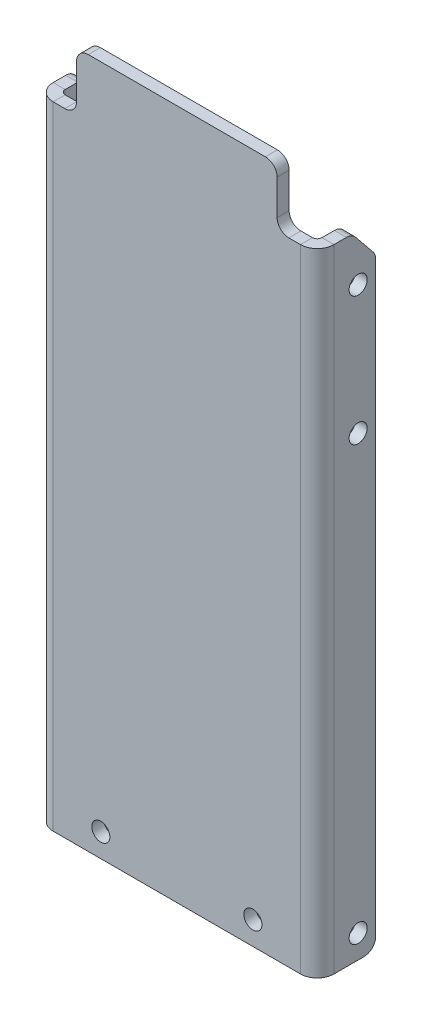
SolidWorks part; units mm, degrees
note: The reader was unsure of these and kept them because the rebuilt part matched: flange length of "Edge-Flange1".
material "5052-H32"
ref_plane "Front Plane" through (0, 0, 0) normal (0, 0, 1) x (1, 0, 0)
ref_plane "Top Plane" through (0, 0, 0) normal (0, 1, 0) x (1, 0, 0)
ref_plane "Right Plane" through (0, 0, 0) normal (1, 0, 0) x (0, 0, -1)
sketch "Sketch1" plane through (0, 0, 0) normal (0, 0, 1) x (1, 0, 0)
  line L0 (-38.1, 0) -> (38.1, 0) construction
  line L1 (-38.1, 124.1214) -> (38.1, 124.1214)
  line L2 (-38.1, 124.1214) -> (-38.1, -47.3286)
  line L3 (-38.1, -47.3286) -> (38.1, -47.3286)
  line L4 (38.1, 124.1214) -> (38.1, -47.3286)
  point P6 (0, 0)
  dimension "D1" = 47.3286
  dimension "D2" = 76.2
  dimension "D3" = 171.45
base flange "Base-Flange1" sketch "Sketch1" thickness 3.2639 reverse thickness direction no parameters "D1"=1.27
edge flange "Edge-Flange1" sketch "Sketch27" flange profiles "Sketch27", "Sketch28" flange angle 90 flange length 15.875 flange position material inside bend radius 1.27 thickness 3.2639 parameters "D6"=10, "D8"=0.254
sketch "Sketch27" plane through (38.1, 0, -3.2639) normal (-1, 0, 0) x (0, 1, 0)
  line L2 (-47.3286, 0) -> (-47.3286, 12.6111)
  line L3 (-47.3286, 12.6111) -> (124.1214, 12.6111)
  line L4 (124.1214, 12.6111) -> (124.1214, 0)
  line L5 (124.1214, 0) -> (-47.3286, 0) construction
  line L6 (124.1214, 0) -> (-47.3286, 0)
sketch "Sketch28" plane through (-38.1, 0, -3.2639) normal (1, 0, 0) x (0, -1, 0)
  line L0 (47.3286, 0) -> (-124.1214, 0) construction
  line L1 (47.3286, 0) -> (-124.1214, 0)
  line L2 (47.3286, 0) -> (47.3286, 12.6111)
  line L3 (47.3286, 12.6111) -> (-124.1214, 12.6111)
  line L4 (-124.1214, 12.6111) -> (-124.1214, 0)
bend "EdgeBend1" bend radius 1.27 bend angle 90 parameters "D5"=1
bend "EdgeBend2" bend radius 1.27 bend angle 90 parameters "D5"=2
sketch "Sketch29" plane through (38.1, 0, 0) normal (1, 0, 0) x (0, 0, -1)
  line L0 (11.1125, 76.4964) -> (11.1125, -40.9786) construction
  line L1 (15.875, -47.3286) -> (4.5339, -47.3286) construction
  line L3 (0, -47.3286) -> (0, 124.1214) construction
  point P4 (11.1125, 111.4214)
  dimension "D1" = 6.35
  dimension "D2" = 117.475
  dimension "D3" = 11.1125
  dimension "D4" = 34.925
hole_wizard "#10 (0.1935) Diameter Hole1" positions "Sketch30" profile "Sketch31" hole size "#10" standard "ANSI Inch" end condition through all
sketch "Sketch30" plane through (38.1, 0, 0) normal (1, 0, 0) x (0, 0, -1)
  point P0 (11.1125, 76.4964)
  point P3 (11.1125, -40.9786)
  point P6 (11.1125, 111.4214)
sketch "Sketch31" plane through (38.1, 76.4964, -11.1125) normal (0, 1, 0) x (0, 0, -1)
  line L0 (0, 0) -> (0, 76.2)
  line L1 (0, 76.2) -> (2.4574, 76.2)
  line L2 (2.4574, 76.2) -> (2.4574, 0)
  line L5 (2.4574, 0) -> (0, 0)
  line L11 (0, -6.35) -> (0, 107.95) construction
  dimension "Thru Hole Dia." = 4.9149
  dimension "Thru Hole Depth" = 76.2
sketch "Sketch33" plane through (0, 0, 0) normal (0, 0, 1) x (1, 0, 0)
  line L0 (33.5661, 124.1214) -> (-33.5661, 124.1214) construction
  line L1 (-27.2161, 124.1214) -> (27.2161, 124.1214)
  line L2 (-27.2161, 124.1214) -> (-27.2161, 139.9964)
  line L3 (-27.2161, 139.9964) -> (27.2161, 139.9964)
  line L4 (27.2161, 124.1214) -> (27.2161, 139.9964)
  line L5 (-33.5661, 124.1214) -> (-33.5661, -47.3286) construction
  point P9 (0, 124.1214)
  dimension "D1" = 15.875
  dimension "D2" = 6.35
extrude "Boss-Extrude1" add sketch "Sketch33" against normal up to surface (3.2639 mm away) up to face at (0, 38.3964, -3.2639)
chamfer "Chamfer1" distance 7.9375 angle 39 2 edges at (-36.4681, 124.1214, -15.875) (36.4681, 124.1214, -15.875)
sketch "Sketch34" plane through (0, 0, 0) normal (0, 0, 1) x (1, 0, 0)
  line L0 (-20.6375, -40.9786) -> (20.6375, -40.9786) construction
  line L1 (-33.5661, -47.3286) -> (33.5661, -47.3286) construction
  point P2 (0, -40.9786)
  dimension "D1" = 6.35
  dimension "D2" = 41.275
hole_wizard "#10 (0.1935) Diameter Hole2" positions "Sketch35" profile "Sketch36" hole size "#10" standard "ANSI Inch" end condition up to next
sketch "Sketch35" plane through (0, 0, 0) normal (0, 0, 1) x (1, 0, 0)
  point P0 (-20.6375, -40.9786)
  point P3 (20.6375, -40.9786)
sketch "Sketch36" plane through (-20.6375, -40.9786, 0) normal (1, 0, 0) x (0, -1, 0)
  line L0 (0, 0) -> (0, 3.2639)
  line L1 (0, 3.2639) -> (2.4574, 3.2639)
  line L2 (2.4574, 3.2639) -> (2.4574, 0)
  line L5 (2.4574, 0) -> (0, 0)
  line L11 (0, -6.35) -> (0, 107.95) construction
  dimension "Thru Hole Dia." = 4.9149
  dimension "Thru Hole Depth" = 3.2639
fillet "Fillet1" radius 3.175 10 edges at (36.4681, 116.1839, -15.875) (36.468, 124.1214, -9.4473) (-36.4681, 116.1839, -15.875) (-36.4681, 124.1214, -9.4473) (-27.2161, 124.1214, -1.632) (27.2161, 124.1214, -1.632) (-36.4681, -47.3286, -15.875) (36.4681, -47.3286, -15.875) (-27.2161, 139.9964, -1.632) (27.2161, 139.9964, -1.632)
sketch "Bend-Lines1" [suppressed] plane through (0, 0, 0) normal (0, 1, 0) x (1, 0, 0)
sketch "Bounding-Box1" [suppressed] plane through (0, 0, 0) normal (0, 1, 0) x (1, 0, 0)
sheet metal parameters "Sheet-Metal1" thickness 3.2639 parameters "D1"=1.27
flat pattern "Flat-Pattern1" [suppressed]
sketch "Bend-Lines2" plane through (0, 0, 0) normal (0, 1, 0) x (1, 0, 0)
sketch3d "Bounding-Box2" [suppressed]
  line L0 (38.1, 56.2696, 0) -> (38.1, -45.3304, 0) construction
  line L1 (-38.1, 56.2696, 0) -> (-38.1, -45.3304, 0) construction
  line L2 (38.1, 56.2696, 0) -> (-38.1, 56.2696, 0) construction
  line L3 (38.1, -45.3304, 0) -> (-38.1, -45.3304, 0) construction
sheet metal parameters "Sheet-Metal8" thickness 3.2639 parameters "D1"=1.27
flat pattern "Flat-Pattern1"
sketch "Bend-Lines2" plane through (0, 0, 0) normal (0, 0, 1) x (1, 0, 0)
  line L0 (-35.8453, 56.2696) -> (-35.8453, -45.3304) construction
  line L1 (35.8453, -45.3304) -> (35.8453, 56.2696) construction
  line L2 (-35.8453, 56.2696) -> (-35.8453, -45.3304) construction
  line L3 (35.8453, -45.3304) -> (35.8453, 56.2696) construction
sketch3d "Bounding-Box2" [suppressed]
  line L0 (49.4656, 56.2696, 0) -> (49.4656, -45.3304, 0) construction
  line L1 (-49.4656, 56.2696, 0) -> (-49.4656, -45.3304, 0) construction
  line L2 (49.4656, 56.2696, 0) -> (-49.4656, 56.2696, 0) construction
  line L3 (49.4656, -45.3304, 0) -> (-49.4656, -45.3304, 0) construction
bend of the flat pattern "Flatten-<EdgeBend1>1"
bend of the flat pattern "Flatten-<EdgeBend2>1"
sheet metal parameters "Sheet-Metal9" thickness 3.2639 parameters "D1"=1.27
flat pattern "Flat-Pattern1" [suppressed]
sketch "Bend-Lines2" plane through (0, 0, 0) normal (0, 0, 1) x (1, 0, 0)
  line L0 (-35.8453, 126.1196) -> (-35.8453, -45.3304) construction
  line L1 (35.8453, -45.3304) -> (35.8453, 126.1196) construction
  line L2 (-35.8453, 126.1196) -> (-35.8453, -45.3304) construction
  line L3 (35.8453, -45.3304) -> (35.8453, 126.1196) construction
sketch3d "Bounding-Box2" [suppressed]
  line L0 (49.4656, 126.1196, 0) -> (49.4656, -45.3304, 0) construction
  line L1 (-49.4656, 126.1196, 0) -> (-49.4656, -45.3304, 0) construction
  line L2 (49.4656, 126.1196, 0) -> (-49.4656, 126.1196, 0) construction
  line L3 (49.4656, -45.3304, 0) -> (-49.4656, -45.3304, 0) construction
bend of the flat pattern "Flatten-<EdgeBend1>1"
bend of the flat pattern "Flatten-<EdgeBend2>1"
sketch "Sketch29-1" [suppressed] plane through (33.5906, 0, 0) normal (0, 0, 1) x (1, 0, 0)
  line L0 (11.1125, 78.4946) -> (11.1125, -38.9804) construction
  line L1 (15.875, -45.3304) -> (-83.0561, -45.3304) construction
  line L3 (0, -45.3304) -> (0, 126.1196) construction
  point P4 (11.1125, 113.4196)
  dimension "D1" = 6.35
  dimension "D2" = 117.475
  dimension "D3" = 11.1125
  dimension "D4" = 34.925
sheet metal parameters "Sheet-Metal10" thickness 3.2639 parameters "D1"=1.27
flat pattern "Flat-Pattern1" [suppressed]
sketch "Bend-Lines2" plane through (0, 0, 0) normal (0, 0, 1) x (1, 0, 0)
  line L0 (-35.8453, 124.1214) -> (-35.8453, -47.3286) construction
  line L1 (35.8453, -47.3286) -> (35.8453, 124.1214) construction
  line L2 (-35.8453, 124.1214) -> (-35.8453, -47.3286) construction
  line L3 (35.8453, -47.3286) -> (35.8453, 124.1214) construction
sketch3d "Bounding-Box2" [suppressed]
  line L0 (49.4656, 139.9964, 0) -> (49.4656, -47.3286, 0) construction
  line L1 (-49.4656, 139.9964, 0) -> (-49.4656, -47.3286, 0) construction
  line L2 (49.4656, 139.9964, 0) -> (-49.4656, 139.9964, 0) construction
  line L3 (49.4656, -47.3286, 0) -> (-49.4656, -47.3286, 0) construction
bend of the flat pattern "Flatten-<EdgeBend1>1"
bend of the flat pattern "Flatten-<EdgeBend2>1"
sketch "Sketch29-1" [suppressed] plane through (33.5906, 0, 0) normal (0, 0, 1) x (1, 0, 0)
  line L0 (11.1125, 76.4964) -> (11.1125, -40.9786) construction
  line L1 (15.875, -47.3286) -> (-83.0561, -47.3286) construction
  line L3 (0, -47.3286) -> (0, 124.1214) construction
  point P4 (11.1125, 111.4214)
  dimension "D1" = 6.35
  dimension "D2" = 117.475
  dimension "D3" = 11.1125
  dimension "D4" = 34.925
sheet metal parameters "Sheet-Metal11" thickness 3.2639 parameters "D1"=1.27
flat pattern "Flat-Pattern1" [suppressed]
sketch "Bend-Lines2" plane through (0, 0, 0) normal (0, 0, 1) x (1, 0, 0)
  line L0 (-35.8453, 124.1214) -> (-35.8453, -47.3286) construction
  line L1 (35.8453, -47.3286) -> (35.8453, 124.1214) construction
  line L2 (-35.8453, 124.1214) -> (-35.8453, -47.3286) construction
  line L3 (35.8453, -47.3286) -> (35.8453, 124.1214) construction
sketch3d "Bounding-Box2" [suppressed]
  line L0 (49.4655, -47.3286, 0) -> (49.4656, 139.9964, 0) construction
  line L1 (-49.4656, -47.3285, 0) -> (-49.4655, 139.9965, 0) construction
  line L2 (49.4655, -47.3286, 0) -> (-49.4656, -47.3285, 0) construction
  line L3 (49.4656, 139.9964, 0) -> (-49.4655, 139.9965, 0) construction
bend of the flat pattern "Flatten-<EdgeBend1>1"
bend of the flat pattern "Flatten-<EdgeBend2>1"
sketch "Sketch29-1" [suppressed] plane through (33.5906, 0, 0) normal (0, 0, 1) x (1, 0, 0)
  line L0 (11.1125, 76.4964) -> (11.1125, -40.9786) construction
  line L1 (12.7, -47.3286) -> (-79.8811, -47.3286) construction
  line L3 (0, -47.3286) -> (0, 124.1214) construction
  point P4 (11.1125, 111.4214)
  dimension "D1" = 6.35
  dimension "D2" = 117.475
  dimension "D3" = 11.1125
  dimension "D4" = 34.925
